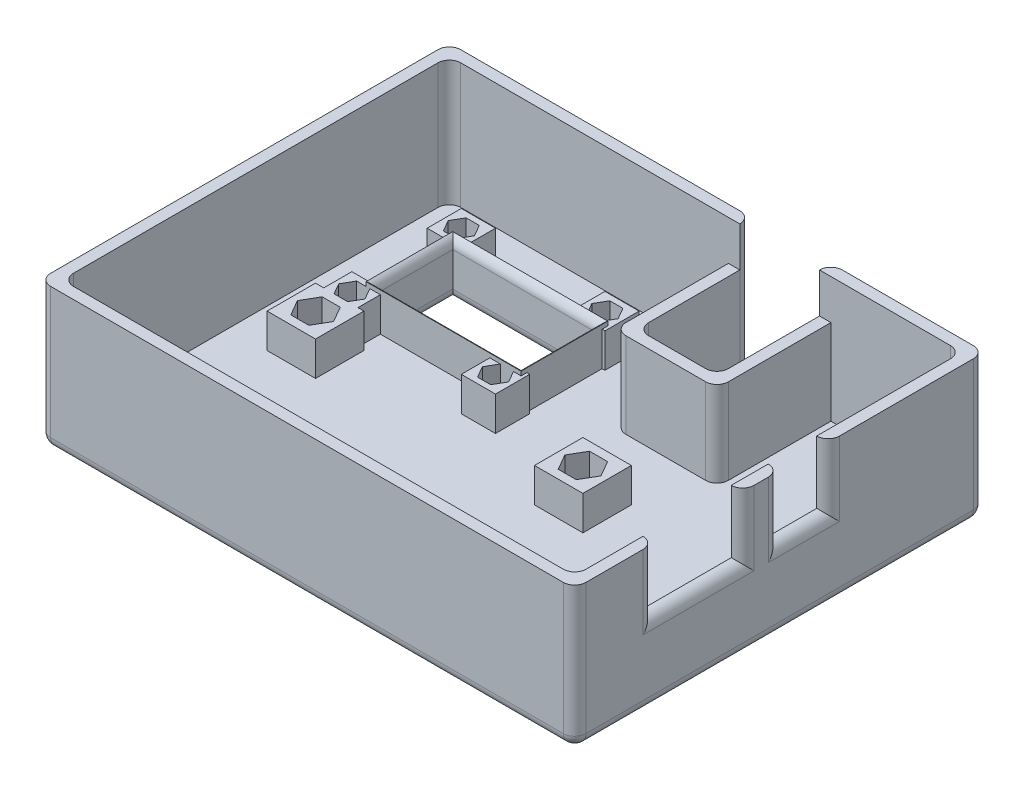
SolidWorks part; units mm, degrees
ref_plane "Plano frontal" through (0, 0, 0) normal (0, 0, 1) x (1, 0, 0)
ref_plane "Plano superior" through (0, 0, 0) normal (0, 1, 0) x (1, 0, 0)
ref_plane "Plano direito" through (0, 0, 0) normal (1, 0, 0) x (0, 0, -1)
sketch "Esboço1" plane through (0, 0, 0) normal (0, 1, 0) x (1, 0, 0)
  line L1 (47, -36) -> (-47, -36)
  line L2 (47, -36) -> (47, 36)
  line L3 (47, 36) -> (-47, 36)
  line L4 (-47, -36) -> (-47, 36)
  line L5 (47, -36) -> (-47, 36) construction
  line L6 (47, 36) -> (-47, -36) construction
  point P0 (0, 0)
  dimension "D1" = 94
  dimension "D2" = 72
extrude "Ressalto-extrusão1" add sketch "Esboço1" along normal mid plane 3
sketch "Esboço2" plane through (0, 1.5, 0) normal (0, 1, 0) x (1, 0, 0)
  line L8 (-45, 34) -> (-45, -34)
  line L9 (-45, -34) -> (45, -34)
  line L10 (45, -34) -> (45, 34)
  line L11 (45, 34) -> (-45, 34)
  line L12 (-45, 34) -> (-45, -34)
  line L13 (-45, -34) -> (45, -34)
  line L14 (45, -34) -> (45, 34)
  line L15 (45, 34) -> (-45, 34)
  line L16 (-47, 36) -> (-47, -36)
  line L17 (-47, -36) -> (47, -36)
  line L18 (47, -36) -> (47, 36)
  line L19 (47, 36) -> (-47, 36)
  line L20 (-47, 36) -> (-47, -36)
  line L21 (-47, -36) -> (47, -36)
  line L22 (47, -36) -> (47, 36)
  line L23 (47, 36) -> (-47, 36)
  dimension "D1" = 2
  dimension "D2" = 0
extrude "Ressalto-extrusão2" add sketch "Esboço2" along normal blind 22
fillet "Filete1" radius 2 8 edges at (45, 12.5, -34) (47, 11, -36) (45, 12.5, 34) (47, 11, 36) (-45, 12.5, 34) (-47, 11, 36) (-47, 11, -36) (-45, 12.5, -34)
sketch "Esboço3" plane through (0, 0, -36) normal (0, 0, -1) x (-1, 0, 0)
  line L0 (-45, 23.5) -> (45, 23.5) construction
  line L1 (-20, 23.5) -> (-6, 23.5)
  line L2 (-20, 23.5) -> (-20, -1.5)
  line L3 (-20, -1.5) -> (-6, -1.5)
  line L4 (-6, 23.5) -> (-6, -1.5)
  line L6 (-45, -1.5) -> (45, -1.5) construction
  line L7 (-45, 23.5) -> (-45, -1.5) construction
  point P8 (0, 0)
  point P9 (-27, -1.5)
  dimension "D1" = 25
  dimension "D2" = 14
extrude "Corte-extrusão1" cut sketch "Esboço3" against normal blind 20
sketch "Esboço4" plane through (0, 1.5, 0) normal (0, 1, 0) x (1, 0, 0)
  line L0 (22, 34) -> (22, 14)
  line L1 (22, 14) -> (4, 14)
  line L2 (4, 14) -> (4, 34)
  line L8 (20, 34) -> (20, 16)
  line L9 (20, 16) -> (6, 16)
  line L10 (6, 16) -> (6, 34)
  line L11 (6, 34) -> (-43, 34)
  line L12 (-45, 32) -> (-45, -32)
  line L13 (-43, -34) -> (43, -34)
  line L14 (45, -32) -> (45, 32)
  line L15 (43, 34) -> (20, 34)
  line L16 (20, 34) -> (20, 16)
  line L17 (20, 16) -> (6, 16)
  line L18 (6, 16) -> (6, 34)
  line L19 (6, 34) -> (4, 34)
  line L23 (22, 34) -> (20, 34)
  arc A4 (-43, 34) -> (-45, 32) centre (-43, 32) ccw
  arc A5 (-45, -32) -> (-43, -34) centre (-43, -32) ccw
  arc A6 (43, -34) -> (45, -32) centre (43, -32) ccw
  arc A7 (45, 32) -> (43, 34) centre (43, 32) ccw
  dimension "D1" = 0
  dimension "D2" = 2
extrude "Ressalto-extrusão3" add sketch "Esboço4" along normal blind 15
sketch "Esboço5" plane through (47, 0, 0) normal (1, 0, 0) x (0, 0, -1)
  line L0 (-34, 23.5) -> (34, 23.5) construction
  line L1 (-22, 23.5) -> (-6.5, 23.5)
  line L2 (-22, 23.5) -> (-22, 12.5)
  line L3 (-22, 12.5) -> (-6.5, 12.5)
  line L4 (-6.5, 23.5) -> (-6.5, 12.5)
  line L6 (-34, 23.5) -> (-34, -1.5) construction
  dimension "D1" = 12
  dimension "D2" = 15.5
  dimension "D3" = 11
extrude "Corte-extrusão2" cut sketch "Esboço5" against normal up to surface (2 mm away) and the other way through all up to face at (45, 12.5, 0)
sketch "Esboço6" plane through (47, 0, 0) normal (1, 0, 0) x (0, 0, -1)
  line L0 (-6.5, 23.5) -> (34, 23.5) construction
  line L1 (0, 23.5) -> (8.5, 23.5)
  line L2 (0, 23.5) -> (0, 12.5)
  line L3 (0, 12.5) -> (8.5, 12.5)
  line L4 (8.5, 23.5) -> (8.5, 12.5)
  line L5 (-34, 23.5) -> (-34, -1.5) construction
  dimension "D1" = 34
  dimension "D2" = 8.5
  dimension "D3" = 11
extrude "Corte-extrusão3" cut sketch "Esboço6" against normal up to surface (2 mm away) up to face at (45, 15.25, 7.125)
fillet "Filete2" radius 2 24 edges at (6, -1.5, -26) (-19.5, -1.5, -36) (-46.4142, -1.5, -35.4142) (-47, -1.5, 0) (-46.4142, -1.5, 35.4142) (0, -1.5, 36) (46.4142, -1.5, 35.4142) (47, -1.5, 0) (46.4142, -1.5, -35.4142) (32.5, -1.5, -36) (20, -1.5, -26) (13, -1.5, -16) (6, 7.5, -16) (20, 7.5, -16) (20, 11, -36) (6, 11, -36) (22, 9, -14) (4, 9, -14) (47, 18, 22) (47, 12.5, 14.25) (47, 18, 6.5) (47, 18, -8.5) (47, 18, 0) (47, 12.5, -4.25)
sketch "Esboço7" plane through (0, 1.5, 0) normal (0, 1, 0) x (1, 0, 0)
  line L0 (-43, -34) -> (43, -34) construction
  line L1 (-35.5877, -22.25) -> (-37.1754, -25)
  line L2 (-37.1754, -25) -> (-35.5877, -27.75)
  line L3 (-35.5877, -27.75) -> (-32.4123, -27.75)
  line L4 (-32.4123, -27.75) -> (-30.8246, -25)
  line L5 (-30.8246, -25) -> (-32.4123, -22.25)
  line L6 (-32.4123, -22.25) -> (-35.5877, -22.25)
  line L7 (-45, 32) -> (-45, -32) construction
  line L8 (-52.3235, -12.75) -> (14.0403, -12.75) construction
  line L9 (-29.75, -29.25) -> (-38.25, -29.25)
  line L10 (-29.75, -29.25) -> (-29.75, -20.75)
  line L11 (-29.75, -20.75) -> (-38.25, -20.75)
  line L12 (-38.25, -29.25) -> (-38.25, -20.75)
  line L13 (-29.75, -29.25) -> (-38.25, -20.75) construction
  line L14 (-29.75, -20.75) -> (-38.25, -29.25) construction
  line L15 (11.3623, -22.25) -> (9.7746, -25)
  line L16 (9.7746, -25) -> (11.3623, -27.75)
  line L17 (11.3623, -27.75) -> (14.5377, -27.75)
  line L18 (14.5377, -27.75) -> (16.1254, -25)
  line L19 (16.1254, -25) -> (14.5377, -22.25)
  line L20 (14.5377, -22.25) -> (11.3623, -22.25)
  line L21 (17.2, -29.25) -> (8.7, -29.25)
  line L22 (17.2, -29.25) -> (17.2, -20.75)
  line L23 (17.2, -20.75) -> (8.7, -20.75)
  line L24 (8.7, -29.25) -> (8.7, -20.75)
  line L25 (17.2, -29.25) -> (8.7, -20.75) construction
  line L26 (17.2, -20.75) -> (8.7, -29.25) construction
  line L27 (17.2, -4.75) -> (8.7, 3.75) construction
  line L28 (17.2, 3.75) -> (8.7, -4.75) construction
  line L29 (-29.75, -4.75) -> (-38.25, 3.75) construction
  line L30 (-29.75, 3.75) -> (-38.25, -4.75) construction
  line L31 (8.7, 3.75) -> (8.7, -4.75)
  line L32 (17.2, -4.75) -> (8.7, -4.75)
  line L33 (17.2, 3.75) -> (17.2, -4.75)
  line L34 (17.2, 3.75) -> (8.7, 3.75)
  line L35 (14.5377, -3.25) -> (11.3623, -3.25)
  line L36 (16.1254, -0.5) -> (14.5377, -3.25)
  line L37 (14.5377, 2.25) -> (16.1254, -0.5)
  line L38 (11.3623, 2.25) -> (14.5377, 2.25)
  line L39 (9.7746, -0.5) -> (11.3623, 2.25)
  line L40 (11.3623, -3.25) -> (9.7746, -0.5)
  line L41 (-38.25, 3.75) -> (-38.25, -4.75)
  line L42 (-29.75, -4.75) -> (-38.25, -4.75)
  line L43 (-29.75, 3.75) -> (-29.75, -4.75)
  line L44 (-29.75, 3.75) -> (-38.25, 3.75)
  line L45 (-32.4123, -3.25) -> (-35.5877, -3.25)
  line L46 (-30.8246, -0.5) -> (-32.4123, -3.25)
  line L47 (-32.4123, 2.25) -> (-30.8246, -0.5)
  line L48 (-35.5877, 2.25) -> (-32.4123, 2.25)
  line L49 (-37.1754, -0.5) -> (-35.5877, 2.25)
  line L50 (-35.5877, -3.25) -> (-37.1754, -0.5)
  circle A0 centre (-34, -25) radius 2.75 construction
  circle A1 centre (12.95, -25) radius 2.75 construction
  circle A2 centre (12.95, -0.5) radius 2.75 construction
  circle A3 centre (-34, -0.5) radius 2.75 construction
  dimension "D1" = 5.5
  dimension "D2" = 9
  dimension "D3" = 11
  dimension "D4" = 1.5
  dimension "D5" = 5.5
  dimension "D6" = 1.5
  dimension "D7" = 9
  dimension "D8" = 46.95
  dimension "D9" = 12.25
extrude "Ressalto-extrusão4" add sketch "Esboço7" along normal blind 6 contours L10 L9 L12 L11 | L1 L2 L3 L4 L5 L6 | L22 L21 L24 L23 | L15 L16 L17 L18 L19 L20 | L41 L42 L43 L44 | L45 L50 L49 L48 L47 L46 | L31 L32 L33 L34 | L35 L40 L39 L38 L37 L36
sketch "Esboço8" plane through (0, 1.5, 0) normal (0, 1, 0) x (1, 0, 0)
  line L0 (6, 34) -> (-43, 34) construction
  line L1 (-34.9547, 26.9) -> (-36.1094, 24.9)
  line L2 (-36.1094, 24.9) -> (-34.9547, 22.9)
  line L3 (-34.9547, 22.9) -> (-32.6453, 22.9)
  line L4 (-32.6453, 22.9) -> (-31.4906, 24.9)
  line L5 (-31.4906, 24.9) -> (-32.6453, 26.9)
  line L6 (-32.6453, 26.9) -> (-34.9547, 26.9)
  line L7 (-45, 32) -> (-45, -32) construction
  line L8 (-30.8, 21.9) -> (-36.8, 21.9)
  line L9 (-30.8, 21.9) -> (-30.8, 27.9)
  line L10 (-30.8, 27.9) -> (-36.8, 27.9)
  line L11 (-36.8, 21.9) -> (-36.8, 27.9)
  line L12 (-30.8, 21.9) -> (-36.8, 27.9) construction
  line L13 (-30.8, 27.9) -> (-36.8, 21.9) construction
  line L14 (4, 34) -> (-43, 34) construction
  line L16 (-9.7347, 26.9) -> (-10.8894, 24.9)
  line L17 (-10.8894, 24.9) -> (-9.7347, 22.9)
  line L18 (-9.7347, 22.9) -> (-7.4253, 22.9)
  line L19 (-7.4253, 22.9) -> (-6.2706, 24.9)
  line L20 (-6.2706, 24.9) -> (-7.4253, 26.9)
  line L21 (-7.4253, 26.9) -> (-9.7347, 26.9)
  line L22 (-5.58, 21.9) -> (-11.58, 21.9)
  line L23 (-5.58, 21.9) -> (-5.58, 27.9)
  line L24 (-5.58, 27.9) -> (-11.58, 27.9)
  line L25 (-11.58, 21.9) -> (-11.58, 27.9)
  line L26 (-5.58, 21.9) -> (-11.58, 27.9) construction
  line L27 (-5.58, 27.9) -> (-11.58, 21.9) construction
  line L28 (-9.7347, 7.68) -> (-10.8894, 5.68)
  line L29 (-10.8894, 5.68) -> (-9.7347, 3.68)
  line L30 (-9.7347, 3.68) -> (-7.4253, 3.68)
  line L31 (-7.4253, 3.68) -> (-6.2706, 5.68)
  line L32 (-6.2706, 5.68) -> (-7.4253, 7.68)
  line L33 (-7.4253, 7.68) -> (-9.7347, 7.68)
  line L34 (-5.58, 2.68) -> (-11.58, 2.68)
  line L35 (-5.58, 2.68) -> (-5.58, 8.68)
  line L36 (-5.58, 8.68) -> (-11.58, 8.68)
  line L37 (-11.58, 2.68) -> (-11.58, 8.68)
  line L38 (-5.58, 2.68) -> (-11.58, 8.68) construction
  line L39 (-5.58, 8.68) -> (-11.58, 2.68) construction
  line L40 (-34.9547, 7.68) -> (-36.1094, 5.68)
  line L41 (-36.1094, 5.68) -> (-34.9547, 3.68)
  line L42 (-34.9547, 3.68) -> (-32.6453, 3.68)
  line L43 (-32.6453, 3.68) -> (-31.4906, 5.68)
  line L44 (-31.4906, 5.68) -> (-32.6453, 7.68)
  line L45 (-32.6453, 7.68) -> (-34.9547, 7.68)
  line L46 (-30.8, 2.68) -> (-36.8, 2.68)
  line L47 (-30.8, 2.68) -> (-30.8, 8.68)
  line L48 (-30.8, 8.68) -> (-36.8, 8.68)
  line L49 (-36.8, 2.68) -> (-36.8, 8.68)
  line L50 (-30.8, 2.68) -> (-36.8, 8.68) construction
  line L51 (-30.8, 8.68) -> (-36.8, 2.68) construction
  circle A0 centre (-33.8, 24.9) radius 2 construction
  circle A1 centre (-8.58, 24.9) radius 2 construction
  circle A2 centre (-8.58, 5.68) radius 2 construction
  circle A3 centre (-33.8, 5.68) radius 2 construction
  point P54 (-33.8, 6.0218)
  point P55 (0, 0)
  dimension "D1" = 4
  dimension "D2" = 1
  dimension "D3" = 11.2
  dimension "D4" = 9.1
  dimension "D5" = 4
  dimension "D6" = 1
  dimension "D7" = 25.22
  dimension "D8" = 9.1
  dimension "D9" = 4
  dimension "D10" = 1
  dimension "D11" = 19.22
  dimension "D12" = 4
  dimension "D13" = 1
extrude "Ressalto-extrusão5" add sketch "Esboço8" along normal blind 6
sketch "Esboço9" plane through (0, 1.5, 0) normal (0, 1, 0) x (1, 0, 0)
  line L0 (-30.8, 21.9) -> (-11.58, 21.9)
  line L9 (-5.58, 21.9) -> (-5.58, 27.9) construction
  line L10 (-30.8, 21.9) -> (-32.3, 21.9)
  line L11 (-11.58, 8.68) -> (-30.8, 8.68)
  line L12 (-7.08, 21.9) -> (-7.08, 8.68)
  line L13 (-11.58, 21.9) -> (-5.58, 21.9) construction
  line L14 (-5.58, 8.68) -> (-11.58, 8.68) construction
  line L18 (-30.8, 8.68) -> (-32.3, 8.68)
  line L19 (-7.08, 8.68) -> (-11.58, 8.68)
  line L20 (-11.58, 21.9) -> (-7.08, 21.9)
  line L31 (-32.3, 21.9) -> (-32.3, 8.68)
  line L32 (-30.8, 22.9) -> (-11.58, 22.9)
  line L33 (-11.58, 22.9) -> (-6.08, 22.9)
  line L34 (-6.08, 22.9) -> (-6.08, 7.68)
  line L35 (-6.08, 7.68) -> (-11.58, 7.68)
  line L36 (-11.58, 7.68) -> (-30.8, 7.68)
  line L37 (-30.8, 7.68) -> (-33.3, 7.68)
  line L38 (-33.3, 22.9) -> (-33.3, 7.68)
  line L39 (-30.8, 22.9) -> (-33.3, 22.9)
  dimension "D1" = 4.5
  dimension "D2" = 1.5
  dimension "D3" = 1
extrude "Ressalto-extrusão6" add sketch "Esboço9" along normal blind 7
sketch "Esboço10" plane through (0, 1.5, 0) normal (0, 1, 0) x (1, 0, 0)
  line L4 (-32.3, 8.68) -> (-7.08, 8.68)
  line L6 (-32.3, 8.68) -> (-7.08, 8.68)
  line L12 (-7.08, 8.68) -> (-7.08, 21.9)
  line L13 (-7.08, 8.68) -> (-7.08, 21.9)
  line L14 (-7.08, 21.9) -> (-32.3, 21.9)
  line L16 (-7.08, 21.9) -> (-32.3, 21.9)
  line L18 (-32.3, 21.9) -> (-32.3, 8.68)
  line L20 (-32.3, 21.9) -> (-32.3, 8.68)
  dimension "D1" = 0
extrude "Corte-extrusão4" cut sketch "Esboço10" against normal up to surface (3 mm away) up to face at (7.8, -1.5, -13.0343)
fillet "Filete3" radius 2 8 edges at (-7.08, 8.5, -15.29) (-7.08, -1.5, -15.29) (-19.69, -1.5, -21.9) (-19.69, 8.5, -21.9) (-19.69, 8.5, -8.68) (-19.69, -1.5, -8.68) (-32.3, -1.5, -15.29) (-32.3, 8.5, -15.29)
